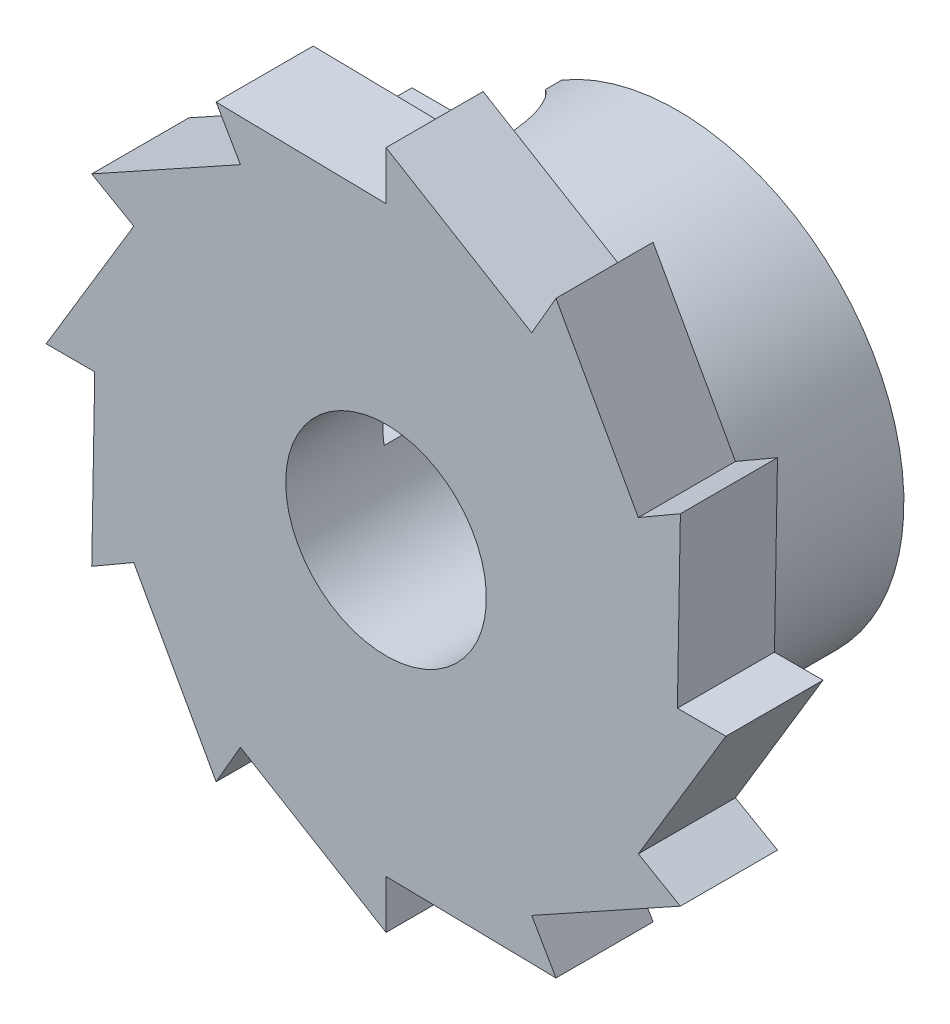
SolidWorks part; units mm, degrees
ref_plane "Front Plane" through (0, 0, 0) normal (0, 0, 1) x (1, 0, 0)
ref_plane "Top Plane" through (0, 0, 0) normal (0, 1, 0) x (1, 0, 0)
ref_plane "Right Plane" through (0, 0, 0) normal (1, 0, 0) x (0, 0, -1)
sketch "Sketch1" plane through (0, 0, 0) normal (0, 0, 1) x (1, 0, 0)
  line L0 (0, 9) -> (0, 10.5)
  line L1 (0.0027, 10.5) -> (-49999.9973, 10.5) construction
  line L2 (0, 0) -> (0, 50000) construction
  line L3 (-0.0178, -0.0309) -> (24999.9822, 43301.2393) construction
  line L4 (0, 9) -> (0, 3.1)
  line L5 (4.5, 7.7942) -> (1.55, 2.6847)
  line L6 (4.5, 7.7942) -> (0, 10.5)
  circle A0 centre (0, 0) radius 9 construction
  circle A1 centre (0, 0) radius 3.1 construction
  arc A2 (0, 10.5) -> (4.5, 7.7942) centre (0, 5.4051) cw construction
  arc A3 (0, 3.1) -> (1.55, 2.6847) centre (0, 0) cw
  dimension "D1" = 6.2
  dimension "D2" = 18
  dimension "D3" = 30
  dimension "D4" = 1.5
extrude "Boss-Extrude1" add sketch "Sketch1" along normal blind 3
pattern_circular "CirPattern1" count 12 over 360 about axis through (0, 0, 3) along (0, 0, -1) of "Boss-Extrude1"
sketch "Sketch3" plane through (0, 0, 0) normal (0, 0, -1) x (-1, 0, 0)
  line L0 (7, -3.5) -> (7, -7)
  line L2 (-7, 0) -> (-7, 7)
  line L3 (-7, 7) -> (7, 7)
  line L5 (7, -7) -> (0, -7)
  line L7 (8.2, 3.5) -> (8.2, -3.5)
  line L8 (8.2, -3.5) -> (7, -3.5)
  line L9 (7, 0) -> (50007, 0) construction
  line L10 (7, 7) -> (8.2, 7)
  line L11 (8.2, 7) -> (8.2, 3.5)
  arc A0 (7, 0) -> (0, -7) centre (0, 0) ccw construction
  arc A1 (0, -7) -> (-7, 0) centre (0, 0) cw
  circle A2 centre (0, 0) radius 3.1
  circle A3 centre (0, 0) radius 3.1 construction
  point P14 (8.2, 0)
  dimension "D1" = 14
  dimension "D2" = 8.2
extrude "Boss-Extrude2" add sketch "Sketch3" along normal blind 6
sketch "Sketch4" plane through (0, 7, 0) normal (0, 1, 0) x (1, 0, 0)
  line L0 (-3.1, 0) -> (3.1, 0) construction
  line L1 (-3.1, 0) -> (3.1, 0) construction
  line L2 (-3.1, 0) -> (-3.1, -50000) construction
  line L4 (-8.2, 3) -> (-3.1, 3) construction
  line L8 (-8.2, 6) -> (-8.2, 0) construction
  circle A1 centre (-5.65, 3) radius 1.5
  point P11 (-5.65, 3)
  dimension "D1" = 3
sketch "Sketch6" plane through (-8.2, 0, 0) normal (-1, 0, 0) x (0, 0, 1)
  line L0 (0, 0) -> (-50000, 0) construction
  line L1 (-6, -0.5) -> (-6, 0.5)
  line L2 (-6, -7) -> (-6, -3.5) construction
  line L3 (-6, 0.5) -> (0, 0.5)
  line L10 (-6, -0.5) -> (0, -0.5)
  line L11 (0, -3.5) -> (0, 3.8252) construction
  line L12 (0, 0.5) -> (0, -0.5)
  point P12 (-0.5, 0)
  dimension "D4" = 0.5
sketch "Sketch9" plane through (0, 7, 0) normal (0, 1, 0) x (1, 0, 0)
  circle A0 centre (-5.65, 3) radius 1.75
  point P0 (-5.65, 3)
  dimension "D1" = 3.5
sketch "Sketch10" plane through (0, 7, 0) normal (0, 1, 0) x (1, 0, 0)
  line L0 (-3.5733, 6) -> (-3.5733, 5.5)
  line L1 (-3.5733, 0.5) -> (-3.5733, 0)
  line L5 (-8.2, 6) -> (7, 6) construction
  line L7 (-8.2, 6) -> (-8.2, 0) construction
  line L8 (-8.2, 5.0149) -> (-8.2, 0.9851)
  line L9 (-5.9339, 0) -> (6.4095, 0) construction
  line L13 (-3.5733, 0) -> (-6.9, 0)
  line L14 (-3.5733, 6) -> (-6.9, 6)
  arc A1 (-6.9, 6) -> (-8.2, 5.0149) centre (-5.65, 3) ccw
  arc A2 (-8.2, 0.9851) -> (-6.9, 0) centre (-5.65, 3) ccw
  arc A3 (-3.5733, 0.5) -> (-3.5733, 5.5) centre (-5.65, 3) ccw
  point P0 (-5.65, 3)
  dimension "D1" = 6.5
  dimension "D2" = 0.5
extrude "Cut-Extrude19" cut sketch "Sketch6" against normal up to surface (5.1406 mm away) up to face at (-3.1, 0, 3)
extrude "Cut-Extrude12" cut sketch "Sketch4" against normal through all
extrude "Cut-Extrude20" cut sketch "Sketch9" against normal up to surface (6.5 mm away) up to face at (-5.65, 0.5, -1.5)
sketch "Sketch12" plane through (0, 0, -6) normal (0, 0, -1) x (-1, 0, 0)
  line L0 (0, 0) -> (50000, 0) construction
  line L1 (8.2, -3.5) -> (6.0622, -3.5) construction
  line L2 (0, -7) -> (7, -7) construction
  line L3 (8.2, 3.5) -> (6.0622, 3.5)
  line L4 (0, -7) -> (7, -7)
  line L5 (7, -7) -> (7, -3.5)
  line L6 (7, -3.5) -> (6.0622, -3.5)
  line L7 (8.2, 3.5) -> (8.2, 7)
  line L8 (8.2, 7) -> (-7, 7)
  line L9 (-7, 7) -> (-7, 0)
  arc A0 (0, -7) -> (6.0622, -3.5) centre (0, 0) ccw
  arc A1 (6.0622, 3.5) -> (-7, 0) centre (0, 0) ccw
  line M9 (8.2, 0.5) -> (8.2, 7)
  line M10 (8.2, 7) -> (-7, 7)
  line M11 (-7, 7) -> (-7, 0)
  line M13 (0, -7) -> (7, -7)
  line M14 (7, -7) -> (7, -3.5)
extrude "Cut-Extrude21" cut sketch "Sketch12" against normal up to surface (6 mm away) contours A1 L8 M11 | A1 L3 M9 M10 | A0 L6 M13 M14 region at (5.4364, 5.4364, -6) region at (-6.0019, 5.597, -6) region at (-5.2918, -5.7512, -6) up to face at (3.8947, -3.9244, 0)
extrude "Cut-Extrude22" cut sketch "Sketch10" against normal up to surface (3.5 mm away) up to face at (-6.9978, 3.5, -3)
equation "\"ratchetTeethCount\"= 12"
equation "\"D3@Sketch1\"=360/\"ratchetTeethCount\""
equation "\"D1@CirPattern1\"=\"ratchetTeethCount\""
equation "\"ratchetHeight\"=1.5"
equation "\"D4@Sketch1\"=\"ratchetHeight\""
equation "\"ratchetInnerDiameter\"= 18"
equation "\"D2@Sketch1\"=\"ratchetInnerDiameter\""
